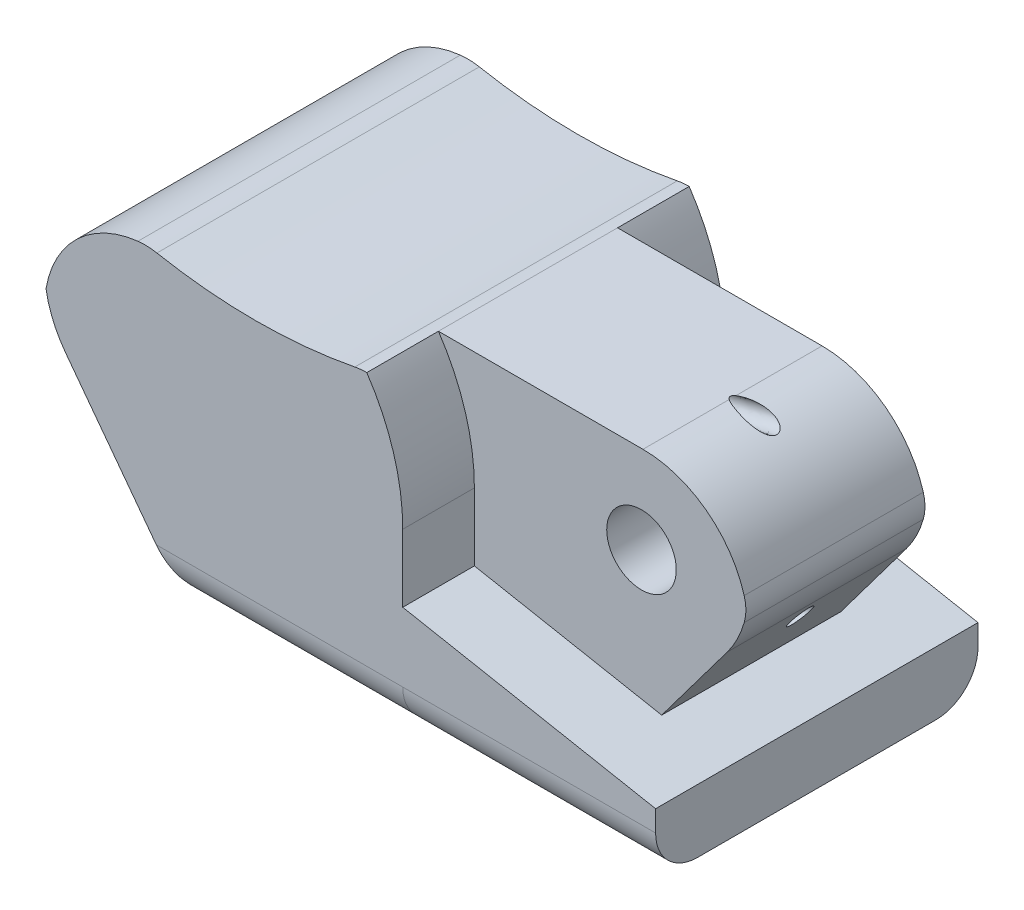
SolidWorks part; units mm, degrees
ref_plane "Front Plane" through (0, 0, 0) normal (0, 0, 1) x (1, 0, 0)
ref_plane "Top Plane" through (0, 0, 0) normal (0, 1, 0) x (1, 0, 0)
ref_plane "Right Plane" through (0, 0, 0) normal (1, 0, 0) x (0, 0, -1)
sketch "Sketch2" plane through (0, 0, 0) normal (0, 0, 1) x (1, 0, 0)
  line L0 (-15, 0) -> (15, 0)
  line L1 (15, 0) -> (15, -5)
  line L2 (15, -5) -> (7.5, -15)
  line L3 (7.5, -15) -> (-7.5, -15)
  line L4 (-7.5, -15) -> (-15, -5)
  line L5 (-15, -5) -> (-15, 0)
  point P0 (0, -15)
  point P4 (0, 0)
  dimension "D1" = 30
  dimension "D2" = 15
  dimension "D3" = 5
  dimension "D4" = 15
extrude "Boss-Extrude1" add sketch "Sketch2" along normal blind 15.3
fillet "Fillet1" radius 5 6 edges at (15, 0, 7.65) (-15, 0, 7.65) (15, -5, 7.65) (7.5, -15, 7.65) (-7.5, -15, 7.65) (-15, -5, 7.65)
sketch "Sketch3" plane through (0, 0, 15.3) normal (0, 0, 1) x (1, 0, 0)
  circle A1 centre (9.9301, -4.1667) radius 1.65
  dimension "D2" = 5
extrude "Cut-Extrude1" cut sketch "Sketch3" against normal through all
ref_plane "Plane1" through (15, 0, 0) normal (1, 0, 0) x (0, 0, -1)
sketch "Sketch4" plane through (15, 0, 0) normal (1, 0, 0) x (0, 0, -1)
  line L0 (0, -6.3333) -> (-15.3, -6.3333) construction
  line L1 (-1006, -4.1667) -> (48994, -4.1667) construction
  line L2 (-7.65, -1006.5012) -> (-7.65, 48993.4988) construction
  line L3 (-15.3, 0) -> (0, 0) construction
  line L4 (-15.3, -4.1667) -> (0, -4.1667) construction
  circle A0 centre (-9.65, -6.1667) radius 0.5
  circle A1 centre (-9.65, -1) radius 0.5
  circle A2 centre (-5.65, -6.1667) radius 0.5
  circle A3 centre (-5.65, -1) radius 0.5
  point P10 (-7.65, -6.3333)
  point P20 (-7.65, -4.1667)
  dimension "D1" = 1
  dimension "D2" = 2
  dimension "D3" = 1
  dimension "D4" = 2
ref_plane "Plane2" through (-15, 0, 0) normal (-1, 0, 0) x (0, 0, 1)
ref_plane "Plane3" through (0, -25, 0) normal (0, -1, 0) x (-1, 0, 0)
sketch "Sketch5" plane through (0, -25, 0) normal (0, -1, 0) x (-1, 0, 0)
  line L0 (5, -15.3) -> (5, 0) construction
  line L1 (5, -3) -> (15, -3)
  line L2 (5, -3) -> (5, -12.3)
  line L3 (5, -12.3) -> (15, -12.3)
  line L4 (15, -3) -> (15, -12.3)
  line L5 (15, -6.6) -> (15, 6.6) construction
  line L6 (14, -15.3) -> (9, -15.3) construction
  dimension "D1" = 3
  dimension "D2" = 3
sketch "Sketch6" plane through (0, 0, 0) normal (0, 1, 0) x (1, 0, 0)
  line L1 (15, -6.6) -> (15, 6.6) construction
  line L2 (2, -3.4) -> (15, -3.4)
  line L3 (2, -3.4) -> (2, 0)
  line L4 (2, 0) -> (15, 0)
  line L5 (15, -3.4) -> (15, 0)
  line L6 (2, -11.9) -> (15, -11.9)
  line L7 (2, -11.9) -> (2, -15.3)
  line L8 (2, -15.3) -> (15, -15.3)
  line L9 (15, -11.9) -> (15, -15.3)
  line L10 (10, 0) -> (-10, 0) construction
  line L11 (10, -15.3) -> (14.9301, -15.3) construction
  point P12 (15, -13.6)
  dimension "D1" = 13
  dimension "D2" = 3.4
extrude "Cut-Extrude4" cut sketch "Sketch6" against normal blind 12
sketch "Sketch7" plane through (0, 0, 0) normal (0, 0, -1) x (-1, 0, 0)
  line L0 (-2, 0) -> (10, 0) construction
  line L1 (0, 0) -> (10, 0)
  arc A0 (0, 0) -> (10, 0) centre (5, 24.4949) ccw
  arc A1 (14.9301, -4.1667) -> (10, 0) centre (10, -5) ccw construction
  dimension "D1" = 25
extrude "Cut-Extrude5" cut sketch "Sketch7" against normal through all
fillet "Fillet5" radius 3 2 edges at (-10, 0, 7.65) (0, 0, 7.65)
fillet "Fillet7" radius 10 2 edges at (2, 0, 13.6) (2, 0, 1.7)
sketch "Sketch8" plane through (-15, 0, 0) normal (-1, 0, 0) x (0, 0, 1)
  line L0 (7.65, -1015) -> (7.65, 48985) construction
  line L1 (15.3, -15) -> (0, -15) construction
  line L2 (0, -13) -> (15.3, -13) construction
  line L3 (-994, -10.6969) -> (49006, -10.6969) construction
  circle A0 centre (7.65, -12) radius 0.5
  circle A1 centre (9.65, -6.1667) radius 0.5 construction
  circle A2 centre (7.65, -6.5) radius 0.5
  point P5 (7.65, -15)
  dimension "D1" = 5.5
  dimension "D2" = 1
ref_plane "Plane4" through (0, 0, 7.65) normal (0, 0, 1) x (1, 0, 0)
sketch "Sketch13" plane through (0, 0, 7.65) normal (0, 0, 1) x (1, 0, 0)
  line L0 (25.0017, -3.8005) -> (-24.9991, -10.6908) construction
fillet "Fillet8" radius 2 1 edges at (14.9301, -4.1667, 7.65)
sketch "Sketch14" plane through (0, 0, 0) normal (0, 0, -1) x (-1, 0, 0)
  line L1 (16.497, -14.0714) -> (-22.6714, -14.0714)
  line L2 (16.497, -14.0714) -> (16.497, -18.2962)
  line L3 (16.497, -18.2962) -> (-22.6714, -18.2962)
  line L4 (-22.6714, -14.0714) -> (-22.6714, -18.2962)
extrude "Cut-Extrude8" cut sketch "Sketch14" against normal through all
fillet "Fillet10" radius 2 2 edges at (0, -14.0714, 0) (0, -14.0714, 15.3)
sketch "Sketch15" plane through (0, 0, 0) normal (0, 0, -1) x (-1, 0, 0)
  line L0 (-14, -11.0714) -> (-2, -8.793)
  line L1 (-2, -14.0714) -> (-14, -14.0714)
  line L2 (-2, -8.793) -> (-2, -14.0714)
  line L3 (-2, -12) -> (-2, -5.586) construction
  line L4 (-14, -14.0714) -> (-14, -11.0714)
  line L6 (7.9023, -14.0714) -> (-7.9023, -14.0714) construction
  dimension "D1" = 12
  dimension "D2" = 3
extrude "Boss-Extrude2" add sketch "Sketch15" against normal up to vertex (15.3 mm away) up to point (2, -12, 15.3)
fillet "Fillet11" radius 2 1 edges at (8, -14.0714, 0)
fillet "Fillet15" radius 2 1 edges at (8, -14.0714, 15.3)
sketch "Sketch16" plane through (0, 0, 0) normal (0, 1, 0) x (1, 0, 0)
  line L0 (10, -11.9) -> (10, -3.4) construction
  circle A0 centre (4, -7.65) radius 0.75
  point P5 (10, -7.65)
  dimension "D1" = 1.5
  dimension "D2" = 6
sketch "Sketch17" plane through (0, 0, 15.3) normal (0, 0, 1) x (1, 0, 0)
  line L0 (4, 0) -> (-26.7247, -7.4059) construction
  line L1 (4.75, 0) -> (3.25, 0) construction
extrude "Cut-Extrude10" cut sketch "Sketch8" along direction (-0.9722, -0.2343, 0) on the side against the normal through all contours A2
sketch "Sketch18" plane through (0, 0, 15.3) normal (0, 0, 1) x (1, 0, 0)
  line L0 (-15, -12.8966) -> (12.4447, -8.4071) construction
  line L1 (-15, -201015) -> (-15, 248985) construction
  line L2 (14, -6.3333) -> (10.8894, -10.4808) construction
extrude "Cut-Extrude11" cut sketch "Sketch8<5>" along direction (0.9869, 0.1614, 0) on the side against the normal through all contours A0
sketch "Sketch8<5>" plane through (-15, 0, 0) normal (-1, 0, 0) x (0, 0, 1) same geometry as "Sketch8"
sketch "Sketch19" plane through (-12, -9, 0) normal (-0.8, -0.6, 0) x (0, 0, 1)
  line L0 (0.2286, -5) -> (15.0714, -5) construction
  circle A0 centre (7.65, 0.1204) radius 1.5
  point P2 (0, 0)
  point P5 (0, 0)
  point P8 (7.65, -5)
  dimension "D1" = 3
extrude "Cut-Extrude12" cut sketch "Sketch19" along direction (1, 0, 0) on the side against the normal blind 4
